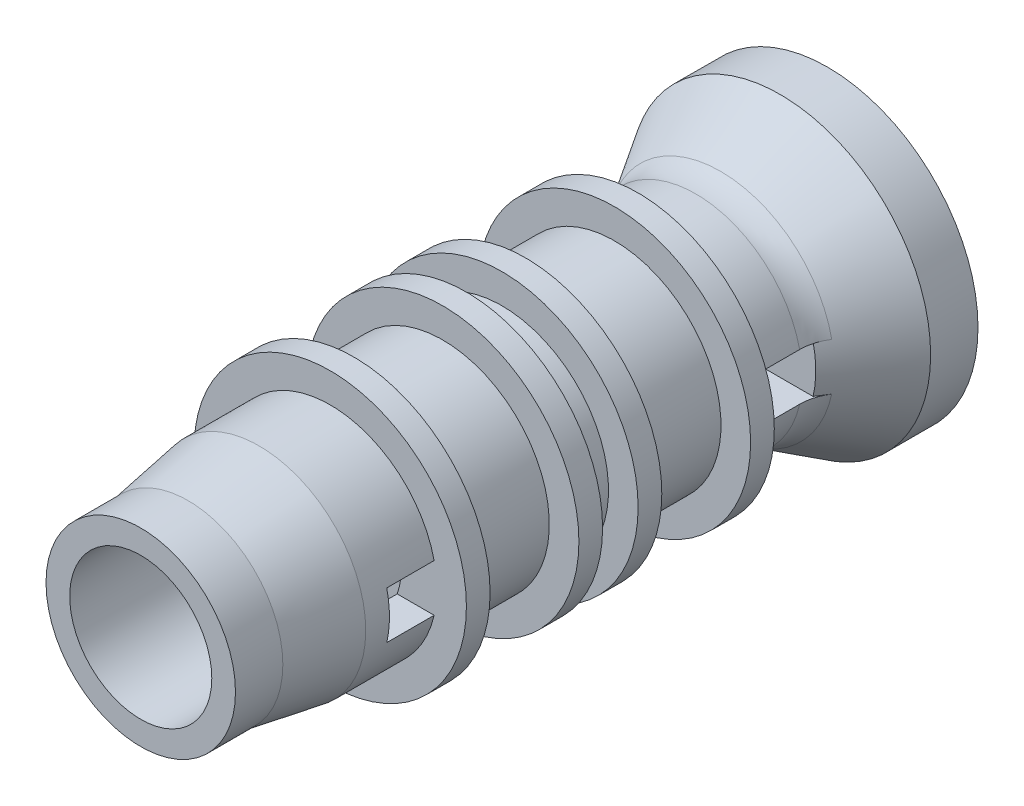
SolidWorks part; units mm, degrees
material "ABS"
ref_plane "正面" through (0, 0, 0) normal (0, 0, 1) x (1, 0, 0)
ref_plane "平面" through (0, 0, 0) normal (0, 1, 0) x (1, 0, 0)
ref_plane "右側面" through (0, 0, 0) normal (1, 0, 0) x (0, 0, -1)
sketch "ｽｹｯﾁ1" plane through (0, 0, 0) normal (0, 0, 1) x (1, 0, 0)
  circle A0 centre (0, 0) radius 4.5 construction
  circle A1 centre (0, 0) radius 6.35
  dimension "D1" = 9
  dimension "D2" = 12.7
ref_plane "平面1" through (0, 0, 5) normal (0, 0, 1) x (1, 0, 0)
sketch "ｽｹｯﾁ2" plane through (0, 0, 5) normal (0, 0, 1) x (1, 0, 0)
  circle A0 centre (0, 0) radius 4.5 construction
  circle A1 centre (0, 0) radius 4.5
ref_plane "平面2" through (0, 0, 29) normal (0, 0, 1) x (1, 0, 0)
ref_plane "平面3" through (0, 0, 24) normal (0, 0, 1) x (1, 0, 0)
sketch "ｽｹｯﾁ5" plane through (0, 0, 29) normal (0, 0, 1) x (1, 0, 0)
  circle A0 centre (0, 0) radius 6.35 construction
  circle A1 centre (0, 0) radius 6.35 construction
  circle A2 centre (0, 0) radius 4
  dimension "D1" = 8
extrude "ﾎﾞｽ - 押し出し3" add sketch "ｽｹｯﾁ2" along normal up to surface (19 mm away) contours A1 up to plane "平面3"
extrude "ﾎﾞｽ - 押し出し4" add sketch "ｽｹｯﾁ1" along normal blind 2 separate body
extrude "ﾎﾞｽ - 押し出し5" add sketch "ｽｹｯﾁ5" against normal blind 2 contours A1
loft "ﾛﾌﾄ1" add section face at (6.35, 0, 2) section face at (4.5, 0, 5)
loft "ﾛﾌﾄ2" add section face at (4.5, 0, 24) section face at (4, 0, 27)
ref_plane "平面5" through (0, 0, 14.5) normal (0, 0, 1) x (1, 0, 0)
ref_plane "平面6" through (0, 0, 15.25) normal (0, 0, 1) x (1, 0, 0)
sketch "ｽｹｯﾁ9" plane through (0, 0, 15.25) normal (0, 0, 1) x (1, 0, 0)
  circle A0 centre (0, 0) radius 5.75
  dimension "D1" = 11.5
extrude "ﾎﾞｽ - 押し出し6" add sketch "ｽｹｯﾁ9" along normal blind 1
ref_plane "平面7" through (0, 0, 20) normal (0, 0, 1) x (1, 0, 0)
sketch "ｽｹｯﾁ10" plane through (0, 0, 20) normal (0, 0, 1) x (1, 0, 0)
  circle A1 centre (0, 0) radius 5.75
  circle A2 centre (0, 0) radius 5.75
  dimension "D1" = 0
extrude "ﾎﾞｽ - 押し出し7" add sketch "ｽｹｯﾁ10" along normal blind 1
mirror "ﾐﾗｰ3" about plane through (0, 0, 14.5) normal (0, 0, 1) of "ﾎﾞｽ - 押し出し7", "ﾎﾞｽ - 押し出し6"
sketch "ｽｹｯﾁ6" plane through (0, 0, 0) normal (0, 0, -1) x (-1, 0, 0)
  circle A0 centre (0, 0) radius 2.75
  dimension "D1" = 5.5
extrude "ｶｯﾄ - 押し出し1" cut sketch "ｽｹｯﾁ6" against normal blind 3
sketch "ｽｹｯﾁ7" plane through (0, 0, 3) normal (0, 0, -1) x (-1, 0, 0)
  circle A0 centre (0, 0) radius 1.8
  dimension "D1" = 3.6
extrude "ｶｯﾄ - 押し出し2" cut sketch "ｽｹｯﾁ7" against normal through all
sketch "ｽｹｯﾁ8" plane through (0, 0, 29) normal (0, 0, 1) x (1, 0, 0)
  circle A0 centre (0, 0) radius 3
  dimension "D1" = 6
extrude "ｶｯﾄ - 押し出し3" cut sketch "ｽｹｯﾁ8" against normal offset from surface (23 mm away) 3 up to face at (-1.8, 0, 3)
ref_plane "平面9" through (-4.5, 0, 0) normal (-1, 0, 0) x (0, 0, 1)
sketch "ｽｹｯﾁ13" plane through (0, 0, 6) normal (0, 0, 1) x (1, 0, 0)
  circle A0 centre (0, 0) radius 1.8 construction
  circle A1 centre (0, 0) radius 3
  circle A2 centre (0, 0) radius 3
  circle A3 centre (0, 0) radius 1.8
  dimension "D1" = 0
extrude "ﾎﾞｽ - 押し出し8" add sketch "ｽｹｯﾁ13" along normal offset from surface (14 mm away) 9 up to face at (3, 0, 29)
sketch "ｽｹｯﾁ11" plane through (-4.5, 0, 0) normal (-1, 0, 0) x (0, 0, 1)
  line L0 (0, 0) -> (29, 0) construction
  line L1 (29, -6.9851) -> (29, 6.9851) construction
  line L2 (5, 4.5) -> (5, -4.5) construction
  line L3 (16.25, 1) -> (18.25, 1)
  line L4 (16.25, 1) -> (16.25, -1)
  line L5 (16.25, -1) -> (18.25, -1)
  line L6 (18.25, 1) -> (18.25, -1)
  line L7 (16.25, 1) -> (18.25, -1) construction
  line L8 (16.25, -1) -> (18.25, 1) construction
  line L9 (7, -1) -> (5, -1)
  line L10 (13.75, 1) -> (15.25, 1)
  line L11 (13.75, 1) -> (13.75, -1)
  line L12 (13.75, -1) -> (15.25, -1)
  line L13 (15.25, 1) -> (15.25, -1)
  line L14 (13.75, 1) -> (15.25, -1) construction
  line L15 (13.75, -1) -> (15.25, 1) construction
  line L16 (7, -1) -> (7, 1)
  line L17 (9, 1) -> (11, 1)
  line L18 (9, 1) -> (9, -1)
  line L19 (9, -1) -> (11, -1)
  line L20 (11, 1) -> (11, -1)
  line L21 (9, 1) -> (11, -1) construction
  line L22 (9, -1) -> (11, 1) construction
  line L23 (9, -4.5) -> (9, 4.5) construction
  line L24 (13.75, -5.75) -> (13.75, 5.75) construction
  line L25 (16.25, -5.75) -> (16.25, 5.75) construction
  line L26 (7, 1) -> (5, 1)
  line L27 (5, -1) -> (5, 1)
  line L28 (7, -1) -> (5, 1) construction
  line L29 (7, 1) -> (5, -1) construction
  line L30 (21, -4.5) -> (21, 4.5) construction
  line L31 (23, -1) -> (21, -1)
  line L32 (23, -1) -> (23, 1)
  line L33 (23, 1) -> (21, 1)
  line L34 (21, -1) -> (21, 1)
  line L35 (23, -1) -> (21, 1) construction
  line L36 (23, 1) -> (21, -1) construction
  point P5 (17.25, 0)
  point P12 (14.5, 0)
  point P19 (10, 0)
  point P26 (6, 0)
  point P33 (22, 0)
  dimension "D1" = 2
  dimension "D2" = 2
  dimension "D3" = 1.5
  dimension "D4" = 2
extrude "ｶｯﾄ - 押し出し4" cut sketch "ｽｹｯﾁ11" against normal up to next
sketch "ｽｹｯﾁ14" plane through (0, 0, 21) normal (0, 0, 1) x (1, 0, 0)
  line L2 (-2.8284, 1) -> (-4.3875, 1) construction
  line L3 (-2.8284, -1) -> (-4.3875, -1) construction
  line L6 (-2.8284, 1) -> (-4.3875, 1) construction
  line L7 (-2.8284, -1) -> (-4.3875, -1) construction
  line L8 (-2.8284, 1) -> (-1.4967, 1)
  line L9 (-2.8284, -1) -> (-1.4967, -1)
  arc A3 (-2.8284, -1) -> (-2.8284, 1) centre (0, 0) cw
  arc A4 (-1.4967, -1) -> (-1.4967, 1) centre (0, 0) cw
extrude "ｶｯﾄ - 押し出し6" cut sketch "ｽｹｯﾁ14" against normal up to surface (14 mm away) up to face at (-3.046, 0, 7)
sketch "ｽｹｯﾁ12" plane through (0, 0, 0) normal (0, 0, -1) x (-1, 0, 0)
  line L0 (0, 0) -> (0, 2.75) construction
  line L1 (0, 0) -> (0.3745, 2.7244) construction
  line L2 (0, 0) -> (0.7419, 2.648) construction
  line L3 (0, 0) -> (1.0956, 2.5223) construction
  line L4 (0, 0) -> (1.4289, 2.3497) construction
  line L5 (0, 0) -> (1.7355, 2.1332) construction
  line L6 (0, 0) -> (2.0098, 1.877) construction
  line L7 (0, 0) -> (2.2467, 1.5859) construction
  line L8 (0, 0) -> (2.4417, 1.2652) construction
  line L9 (0, 0) -> (2.5912, 0.9209) construction
  line L10 (0, 0) -> (2.6925, 0.5595) construction
  line L11 (0, 0) -> (2.7436, 0.1877) construction
  line L12 (0, 0) -> (2.7436, -0.1877) construction
  line L13 (0, 0) -> (2.6925, -0.5595) construction
  line L14 (0, 0) -> (2.5912, -0.9209) construction
  line L15 (0, 0) -> (2.4417, -1.2652) construction
  line L16 (0, 0) -> (2.2467, -1.5859) construction
  line L17 (0, 0) -> (2.0098, -1.877) construction
  line L18 (0, 0) -> (1.7355, -2.1332) construction
  line L19 (0, 0) -> (1.4289, -2.3497) construction
  line L20 (0, 0) -> (1.0956, -2.5223) construction
  line L21 (0, 0) -> (0.7419, -2.648) construction
  line L22 (0, 0) -> (0.3745, -2.7244) construction
  line L23 (0, 0) -> (0, -2.75) construction
  line L24 (0, 0) -> (-0.3745, -2.7244) construction
  line L25 (0, 0) -> (-0.7419, -2.648) construction
  line L26 (0, 0) -> (-1.0956, -2.5223) construction
  line L27 (0, 0) -> (-1.4289, -2.3497) construction
  line L28 (0, 0) -> (-1.7355, -2.1332) construction
  line L29 (0, 0) -> (-2.0098, -1.877) construction
  line L30 (0, 0) -> (-2.2467, -1.5859) construction
  line L31 (0, 0) -> (-2.4417, -1.2652) construction
  line L32 (0, 0) -> (-2.5912, -0.9209) construction
  line L33 (0, 0) -> (-2.6925, -0.5595) construction
  line L34 (0, 0) -> (-2.7436, -0.1877) construction
  line L35 (0, 0) -> (-2.7436, 0.1877) construction
  line L36 (0, 0) -> (-2.6925, 0.5595) construction
  line L37 (0, 0) -> (-2.5912, 0.9209) construction
  line L38 (0, 0) -> (-2.4417, 1.2652) construction
  line L39 (0, 0) -> (-2.2467, 1.5859) construction
  line L40 (0, 0) -> (-2.0098, 1.877) construction
  line L41 (0, 0) -> (-1.7355, 2.1332) construction
  line L42 (0, 0) -> (-1.4289, 2.3497) construction
  line L43 (0, 0) -> (-1.0956, 2.5223) construction
  line L44 (0, 0) -> (-0.7419, 2.648) construction
  line L45 (0, 0) -> (-0.3745, 2.7244) construction
  line L46 (0, 0) -> (0.2081, 3.0429) construction
  line L47 (0.2081, 3.0429) -> (-0.0626, 2.7493)
  line L48 (-0.0626, 2.7493) -> (0, 0) construction
  line L49 (0, 0) -> (0.4364, 2.7152) construction
  line L50 (0.4364, 2.7152) -> (0.2081, 3.0429)
  line L51 (1.0214, 2.8739) -> (0.6815, 2.6642)
  line L52 (1.1527, 2.4967) -> (1.0214, 2.8739)
  line L53 (1.7589, 2.4918) -> (1.375, 2.3816)
  line L54 (1.7836, 2.0931) -> (1.7589, 2.4918)
  line L55 (2.3659, 1.9248) -> (1.9666, 1.9223)
  line L56 (2.2822, 1.5343) -> (2.3659, 1.9248)
  line L57 (2.7975, 1.2151) -> (2.4123, 1.3204)
  line L58 (2.6115, 0.8617) -> (2.7975, 1.2151)
  line L59 (3.0216, 0.4153) -> (2.679, 0.6206)
  line L60 (2.7472, 0.1252) -> (3.0216, 0.4153)
  line L61 (3.0216, -0.4153) -> (2.7472, -0.1252)
  line L62 (2.679, -0.6206) -> (3.0216, -0.4153)
  line L63 (2.7975, -1.2151) -> (2.6115, -0.8617)
  line L64 (2.4123, -1.3204) -> (2.7975, -1.2151)
  line L65 (2.3659, -1.9248) -> (2.2822, -1.5343)
  line L66 (1.9666, -1.9223) -> (2.3659, -1.9248)
  line L67 (1.7589, -2.4918) -> (1.7836, -2.0931)
  line L68 (1.375, -2.3816) -> (1.7589, -2.4918)
  line L69 (1.0214, -2.8739) -> (1.1527, -2.4967)
  line L70 (0.6815, -2.6642) -> (1.0214, -2.8739)
  line L71 (0.2081, -3.0429) -> (0.4364, -2.7152)
  line L72 (-0.0626, -2.7493) -> (0.2081, -3.0429)
  line L73 (-0.6205, -2.9862) -> (-0.3123, -2.7322)
  line L74 (-0.802, -2.6304) -> (-0.6205, -2.9862)
  line L75 (-1.4032, -2.708) -> (-1.0379, -2.5466)
  line L76 (-1.482, -2.3165) -> (-1.4032, -2.708)
  line L77 (-2.0818, -2.229) -> (-1.6865, -2.1722)
  line L78 (-2.052, -1.8308) -> (-2.0818, -2.229)
  line L79 (-2.606, -1.5847) -> (-2.21, -1.6366)
  line L80 (-2.4699, -1.2093) -> (-2.606, -1.5847)
  line L81 (-2.9369, -0.8229) -> (-2.5696, -0.9797)
  line L82 (-2.7045, -0.4981) -> (-2.9369, -0.8229)
  line L83 (-3.05, 0) -> (-2.7386, -0.2501)
  line L84 (-2.7386, 0.2501) -> (-3.05, 0)
  line L85 (-2.9369, 0.8229) -> (-2.7045, 0.4981)
  line L86 (-2.5696, 0.9797) -> (-2.9369, 0.8229)
  line L87 (-2.606, 1.5847) -> (-2.4699, 1.2093)
  line L88 (-2.21, 1.6366) -> (-2.606, 1.5847)
  line L89 (-2.0818, 2.229) -> (-2.052, 1.8308)
  line L90 (-1.6865, 2.1722) -> (-2.0818, 2.229)
  line L91 (-1.4032, 2.708) -> (-1.482, 2.3165)
  line L92 (-1.0379, 2.5466) -> (-1.4032, 2.708)
  line L93 (-0.6205, 2.9862) -> (-0.802, 2.6304)
  line L94 (-0.3123, 2.7322) -> (-0.6205, 2.9862)
  circle A0 centre (0, 0) radius 2.75 construction
  circle A1 centre (0, 0) radius 3.05 construction
  arc A2 (0, 2.75) -> (0.3745, 2.7244) centre (0, 0) cw construction
  circle A3 centre (0, 0) radius 2.75 construction
  arc A4 (-0.0626, 2.7493) -> (0.4364, 2.7152) centre (0, 0) cw
  arc A5 (0.6815, 2.6642) -> (1.1527, 2.4967) centre (0, 0) cw
  arc A6 (1.375, 2.3816) -> (1.7836, 2.0931) centre (0, 0) cw
  arc A7 (1.9666, 1.9223) -> (2.2822, 1.5343) centre (0, 0) cw
  arc A8 (2.4123, 1.3204) -> (2.6115, 0.8617) centre (0, 0) cw
  arc A9 (2.679, 0.6206) -> (2.7472, 0.1252) centre (0, 0) cw
  arc A10 (2.7472, -0.1252) -> (2.679, -0.6206) centre (0, 0) cw
  arc A11 (2.6115, -0.8617) -> (2.4123, -1.3204) centre (0, 0) cw
  arc A12 (2.2822, -1.5343) -> (1.9666, -1.9223) centre (0, 0) cw
  arc A13 (1.7836, -2.0931) -> (1.375, -2.3816) centre (0, 0) cw
  arc A14 (1.1527, -2.4967) -> (0.6815, -2.6642) centre (0, 0) cw
  arc A15 (0.4364, -2.7152) -> (-0.0626, -2.7493) centre (0, 0) cw
  arc A16 (-0.3123, -2.7322) -> (-0.802, -2.6304) centre (0, 0) cw
  arc A17 (-1.0379, -2.5466) -> (-1.482, -2.3165) centre (0, 0) cw
  arc A18 (-1.6865, -2.1722) -> (-2.052, -1.8308) centre (0, 0) cw
  arc A19 (-2.21, -1.6366) -> (-2.4699, -1.2093) centre (0, 0) cw
  arc A20 (-2.5696, -0.9797) -> (-2.7045, -0.4981) centre (0, 0) cw
  arc A21 (-2.7386, -0.2501) -> (-2.7386, 0.2501) centre (0, 0) cw
  arc A22 (-2.7045, 0.4981) -> (-2.5696, 0.9797) centre (0, 0) cw
  arc A23 (-2.4699, 1.2093) -> (-2.21, 1.6366) centre (0, 0) cw
  arc A24 (-2.052, 1.8308) -> (-1.6865, 2.1722) centre (0, 0) cw
  arc A25 (-1.482, 2.3165) -> (-1.0379, 2.5466) centre (0, 0) cw
  arc A26 (-0.802, 2.6304) -> (-0.3123, 2.7322) centre (0, 0) cw
  point P53 (0, 0)
  point P54 (0.1877, 2.7436)
  point P56 (0.1877, 2.7436)
  point P129 (0, 0)
  dimension "D2" = 6.1
  dimension "D3" = 10.435
  dimension "D1" = 46
  dimension "D4" = 23
extrude "ｶｯﾄ - 押し出し5" cut sketch "ｽｹｯﾁ12" against normal up to surface (3 mm away) up to face at (-1.8, 0, 3)
sketch "ｽｹｯﾁ15" plane through (-4.5, 0, 0) normal (-1, 0, 0) x (0, 0, 1)
  line L28 (5, -1) -> (7, -1)
  line L29 (5, 1) -> (5, -1)
  line L30 (7, 1) -> (5, 1)
  line L31 (7, -1) -> (7, 1)
  line L32 (5, -1) -> (7, -1)
  line L33 (5, 1) -> (5, -1)
  line L34 (7, 1) -> (5, 1)
  line L35 (7, -1) -> (7, 1)
  line L36 (21, -1) -> (23, -1)
  line L37 (21, 1) -> (21, -1)
  line L38 (23, 1) -> (21, 1)
  line L39 (23, -1) -> (23, 1)
  line L40 (21, -1) -> (23, -1)
  line L41 (21, 1) -> (21, -1)
  line L42 (23, 1) -> (21, 1)
  line L43 (23, -1) -> (23, 1)
  dimension "D4" = 0
  dimension "D5" = 0
extrude "ｶｯﾄ - 押し出し7" cut sketch "ｽｹｯﾁ15" against normal through all
fillet "ﾌｨﾚｯﾄ1" radius 2 2 edges at (0, -4.5, 5) (0, 4.5, 5)
equation "\"D3@ｽｹｯﾁ12\"=360/23*2/3"
